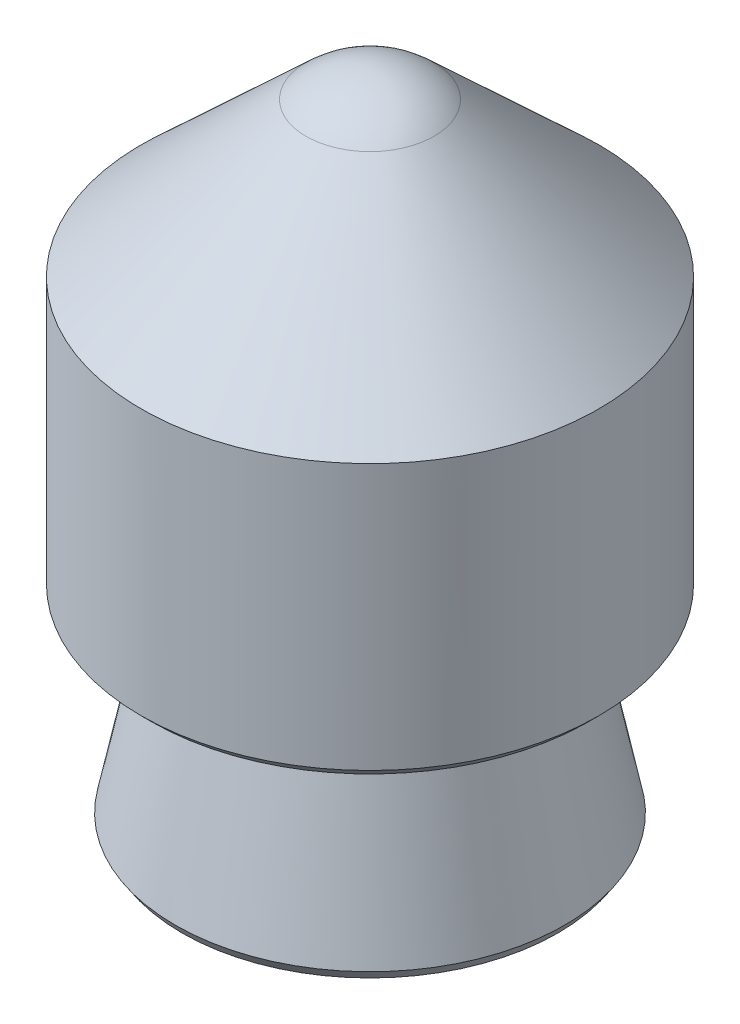
SolidWorks part; units mm, degrees
material "6061-T6 (SS)"
ref_plane "Front Plane" through (0, 0, 0) normal (0, 0, 1) x (1, 0, 0)
ref_plane "Top Plane" through (0, 0, 0) normal (0, 1, 0) x (1, 0, 0)
ref_plane "Right Plane" through (0, 0, 0) normal (1, 0, 0) x (0, 0, -1)
sketch "Sketch1" plane through (0, 0, 0) normal (0, 0, 1) x (1, 0, 0)
  line L0 (0, 25.4) -> (0, 41.3512) construction
  line L2 (4.7085, 14.7066) -> (-4.7085, 14.7066) construction
  line L3 (0, 25.4) -> (-4.8069, 25.4)
  line L4 (-3.8227, 30.2387) -> (-4.8069, 25.4)
  line L5 (0, 25.4) -> (0, 41.3512)
  line L6 (-3.8227, 30.2387) -> (-5.588, 30.2387)
  line L7 (-5.588, 30.2387) -> (-5.588, 36.9824)
  line L8 (-1.5634, 40.7354) -> (-5.588, 36.9824)
  arc A0 (-1.5634, 40.7354) -> (0, 41.3512) centre (0, 39.0588) cw
  dimension "D6" = 2.2923
  dimension "D1" = 26.6446
  dimension "D2" = 3.8227
  dimension "D3" = 11.176
  dimension "D4" = 6.7437
  dimension "D5" = 11.1125
  dimension "D7" = 4.8069
revolve "Revolve1" add sketch "Sketch1" angle 360 about L0
chamfer "Chamfer1" distance 0.254 angle 45 2 edges at (0, 25.4, -4.8069) (0, 30.2387, -5.588) first distance on face at (0, 25.4, -4.8069) first distance on face at (0, 30.2387, -5.588)
sketch "Sketch4" plane through (0, 25.4, 0) normal (0, -1, 0) x (1, 0, 0)
  circle A0 centre (0, 0) radius 3.5
  dimension "D1" = 7
extrude "Cut-Extrude1" cut sketch "Sketch4" against normal blind 2.5
hole_wizard "M7x0.75 Tapped Hole1" positions "Sketch5" profile "Sketch6" tap size "M7x1.0" standard "ANSI Metric"
sketch "Sketch5" plane through (0, 25.4, 0) normal (0, -1, 0) x (-1, 0, 0)
  point P0 (0, 0)
  point P3 (96.1394, -180.6847)
sketch "Sketch6" plane through (0, 25.4, 0) normal (1, 0, 0) x (0, 0, -1)
  line L0 (0, 0) -> (0, 12.7566)
  line L1 (0, 12.7566) -> (3, 10.954)
  line L2 (3, 10.954) -> (3, 0)
  line L5 (3, 0) -> (0, 0)
  line L10 (0, 12.7566) -> (-3, 10.954) construction
  line L11 (0, -6.35) -> (0, 107.95) construction
  dimension "Tap Drill Dia." = 6
  dimension "Tap Drill Depth" = 10.954
  dimension "Drill Angle" = 118
cosmetic thread "Hole Thread1"
